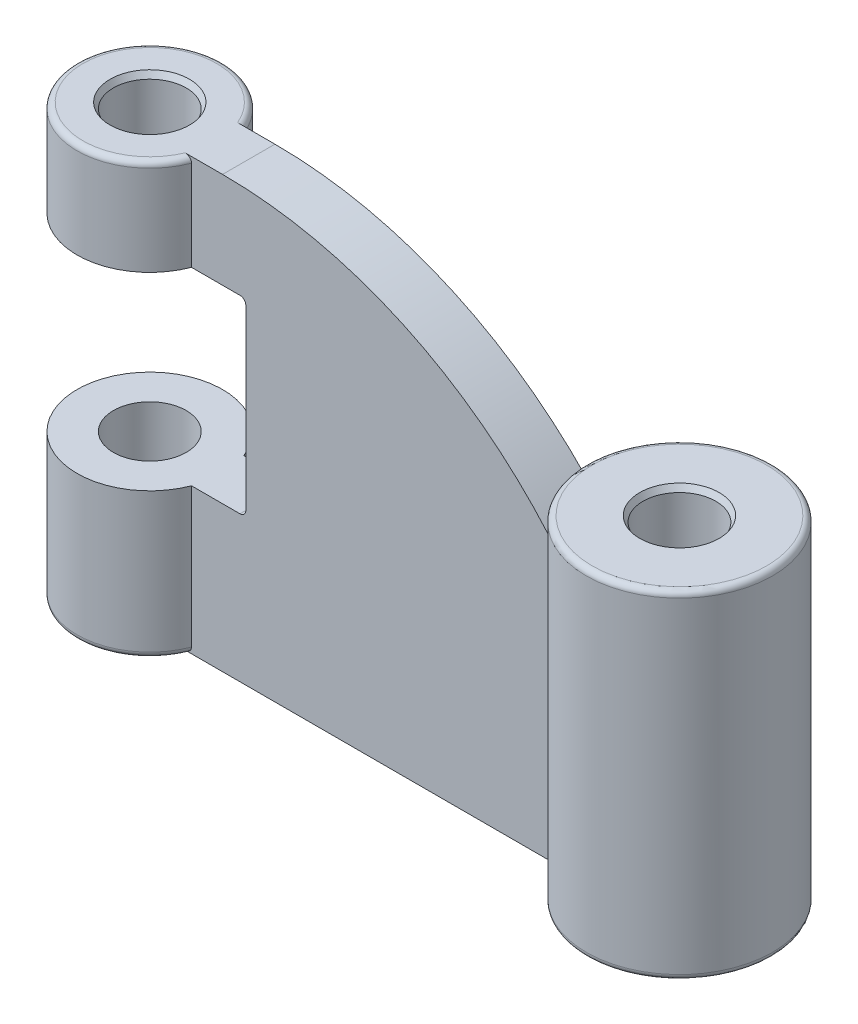
SolidWorks part; units mm, degrees
material "1060 Alloy"
ref_plane "Front Plane" through (0, 0, 0) normal (0, 0, 1) x (1, 0, 0)
ref_plane "Top Plane" through (0, 0, 0) normal (0, 1, 0) x (1, 0, 0)
ref_plane "Right Plane" through (0, 0, 0) normal (1, 0, 0) x (0, 0, -1)
sketch "Sketch1" plane through (0, 0, 0) normal (0, 0, 1) x (1, 0, 0)
  line L1 (148, 0) -> (148, 108.5119) construction
  line L7 (160.5, 116) -> (180, 116)
  line L8 (160.5, 116) -> (160.5, 0)
  line L9 (160.5, 0) -> (180, 0)
  line L10 (180, 116) -> (180, 0)
  dimension "D4" = 25
  dimension "D5" = 64
  dimension "D6" = 116
  dimension "D7" = 148
revolve "Revolve2" add sketch "Sketch1" angle 360 about L1
sketch "Sketch3" plane through (0, 0, 0) normal (0, 0, 1) x (1, 0, 0)
  line L0 (-34, 0) -> (-34, 103.5252) construction
  line L1 (148, 0) -> (148, 108.5119) construction
  line L2 (-46.5, 148) -> (-59, 148)
  line L3 (-46.5, 148) -> (-46.5, 0)
  line L4 (-46.5, 0) -> (-59, 0)
  line L5 (-59, 148) -> (-59, 0)
  dimension "D1" = 25
  dimension "D2" = 50
  dimension "D3" = 182
  dimension "D4" = 148
revolve "Revolve3" add sketch "Sketch3" angle 360 about L0
chamfer "Chamfer2" distance 2 angle 30 2 edges at (148, 116, -12.5) (148, 0, -12.5) first distance on face at (148, 0, -12.5) first distance on face at (148, 0, -32)
fillet "Fillet1" radius 2 2 edges at (-34, 148, -25) (-34, 0, -25)
fillet "Fillet2" radius 2 1 edges at (148, 0, -32)
fillet "Fillet3" radius 2 1 edges at (148, 116, -32)
sketch "Sketch4" plane through (0, 0, 0) normal (0, 0, 1) x (1, 0, 0)
  line L5 (0, 0) -> (-15.0918, 0)
  line L6 (-15.0918, 0) -> (-15.0918, 148)
  line L7 (-15.0918, 148) -> (0, 148)
  line L8 (125.5616, 78.3472) -> (125.5616, 0)
  line L9 (125.5616, 0) -> (0, 0)
  arc A1 (0, 148) -> (125.5616, 78.3472) centre (0, 0) cw
  point P7 (0, 0)
  dimension "D1" = 148
extrude "Boss-Extrude1" add sketch "Sketch4" along normal blind 9 and the other way blind 9
chamfer "Chamfer1" distance 2 angle 30 2 edges at (-34, 0, -12.5) (-34, 148, -12.5) first distance on face at (56.887, 0, 0) first distance on face at (-34, 148, -12.5)
sketch "Sketch23" plane through (0, 0, 0) normal (0, 0, 1) x (1, 0, 0)
  line L0 (-59, 148) -> (-59, 0) construction
  line L1 (-59, 50) -> (6, 50)
  line L2 (-59, 50) -> (-59, 115)
  line L3 (-59, 115) -> (6, 115)
  line L4 (8, 52) -> (8, 113)
  arc A0 (6, 50) -> (8, 52) centre (6, 52) ccw
  arc A1 (6, 115) -> (8, 113) centre (6, 113) cw
  point P9 (8, 50)
  point P12 (8, 115)
  dimension "D4" = 2
  dimension "D1" = 65
  dimension "D2" = 50
  dimension "D3" = 8
extrude "Cut-Extrude9" cut sketch "Sketch23" against normal through all both and the other way through all
equation "\"A\" = 148"
equation "\"D\" = 25"
equation "\"B\" = 64"
equation "\"Y\" = 1.5 * \"B\" + 20"
equation "\"D4@Sketch1\"=\"D\""
equation "\"D5@Sketch1\"=\"B\""
equation "\"D6@Sketch1\"=\"Y\""
equation "\"D7@Sketch1\"=\"A\""
equation "\"C\" = 182"
equation "\"D1@Sketch3\"=\"D\""
equation "\"D3@Sketch3\"=\"C\""
equation "\"D4@Sketch3\"=\"A\""
equation "\"D1@Sketch4\"=\"A\""
equation "\"D1@Sketch8\"=\"A\""
equation "\"Z\"= 2 * \"D\""
equation "\"D2@Sketch22\"=\"Z\""
